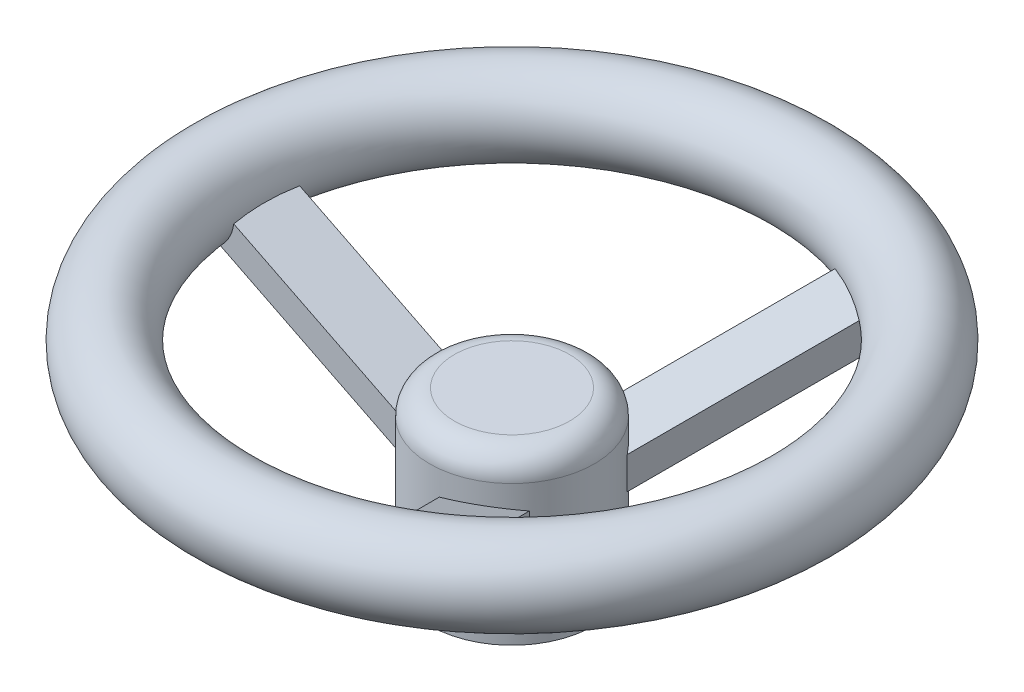
SolidWorks part; units mm, degrees
ref_plane "Front Plane" through (0, 0, 0) normal (0, 0, 1) x (1, 0, 0)
ref_plane "Top Plane" through (0, 0, 0) normal (0, 1, 0) x (1, 0, 0)
ref_plane "Right Plane" through (0, 0, 0) normal (1, 0, 0) x (0, 0, -1)
sketch "Sketch1" plane through (0, 0, 0) normal (0, 1, 0) x (1, 0, 0)
  circle A0 centre (0, 0) radius 8
  circle A1 centre (0, 0) radius 20
  dimension "D1" = 16
  dimension "D2" = 40
extrude "Boss-Extrude1" add sketch "Sketch1" along normal blind 40 contours A1
extrude "Cut-Extrude4" cut sketch "Sketch1<7>" along normal blind 22 contours A0 region at (0, 0, 0)
sketch "Sketch1<7>" plane through (0, 0, 0) normal (0, 1, 0) x (1, 0, 0) same geometry as "Sketch1"
sketch "Sketch3" plane through (0, 0, 0) normal (0, 0, 1) x (1, 0, 0)
  line L0 (0, 15) -> (-70, 50) construction
  line L1 (-20, 0) -> (20, 0) construction
  line L2 (0, 40) -> (0, 62.5735) construction
  line L3 (20, 40) -> (-20, 40) construction
  circle A0 centre (-70, 50) radius 10
  point P12 (-70, 50)
  dimension "D5" = 20
  dimension "D1" = 15
  dimension "D2" = 50
  dimension "D3" = 70
ref_plane "Plane1" through (0, 50, 0) normal (0, 1, 0) x (1, 0, 0)
revolve "Revolve1" add sketch "Sketch3" angle 360 about L2 region at (-70, 50, 0)
ref_plane "Plane2" through (-70, 50, 0) normal (-0.8944, 0.4472, 0) x (0, 0, 1)
sketch "Sketch6" plane through (-70, 50, 0) normal (-0.8944, 0.4472, 0) x (0, 0, 1)
  line L1 (-8, -3.5) -> (8, -3.5)
  line L2 (-8, -3.5) -> (-8, 3.5)
  line L3 (-8, 3.5) -> (8, 3.5)
  line L4 (8, -3.5) -> (8, 3.5)
  line L5 (-8, -3.5) -> (8, 3.5) construction
  line L6 (-8, 3.5) -> (8, -3.5) construction
  point P0 (0, 0)
  dimension "D1" = 7
  dimension "D2" = 16
extrude "Boss-Extrude2" add sketch "Sketch6" against normal up to surface (59.5185 mm away) up to face at (0, 40, 20)
pattern_circular "CirPattern1" count 3 over 360 about axis through (0, 40, 0) along (0, 1, 0) of "Boss-Extrude2" reverse direction yes
fillet "Fillet1" radius 6 1 edges at (0, 40, 20)
